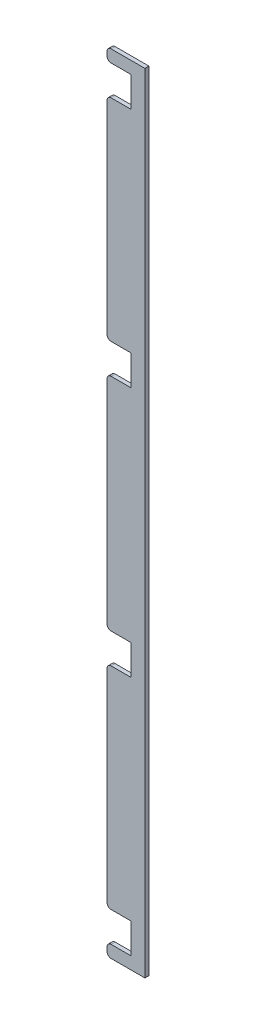
SolidWorks part; units mm, degrees
ref_plane "Front Plane" through (0, 0, 0) normal (0, 0, 1) x (1, 0, 0)
ref_plane "Top Plane" through (0, 0, 0) normal (0, 1, 0) x (1, 0, 0)
ref_plane "Right Plane" through (0, 0, 0) normal (1, 0, 0) x (0, 0, -1)
sketch "Sketch1" plane through (0, 0, 0) normal (0, 0, 1) x (1, 0, 0)
  line L0 (0, -182.5952) -> (-4.5, -182.5952)
  line L2 (0, 13.4048) -> (0, -182.5952)
  line L6 (-4.5, 10.3548) -> (-3.5, 10.3548)
  line L7 (-3.5, 10.3548) -> (-3.5, 2.8548)
  line L9 (-3.5, 2.8548) -> (-4.5, 2.8548)
  line L10 (-4.5, -49.6452) -> (-3.5, -49.6452)
  line L11 (-3.5, -49.6452) -> (-3.5, -57.1452)
  line L12 (-3.5, -57.1452) -> (-4.5, -57.1452)
  line L13 (-4.5, -112.0452) -> (-3.5, -112.0452)
  line L14 (-3.5, -112.0452) -> (-3.5, -119.5452)
  line L15 (-3.5, -119.5452) -> (-4.5, -119.5452)
  line L16 (-4.5, -172.0452) -> (-3.5, -172.0452)
  line L17 (-3.5, -172.0452) -> (-3.5, -179.5452)
  line L18 (-3.5, -179.5452) -> (-4.5, -179.5452)
  line L144 (-8.4, 10.3548) -> (-4.5, 10.3548)
  line L145 (-4.5, 10.3548) -> (-4.5, 2.8548)
  line L146 (-4.5, 2.8548) -> (-8.4, 2.8548)
  line L147 (-9.4, 1.8548) -> (-9.4, -48.6452)
  line L148 (-8.4, -49.6452) -> (-4.5, -49.6452)
  line L149 (-4.5, -49.6452) -> (-4.5, -57.1452)
  line L150 (-4.5, -57.1452) -> (-8.4, -57.1452)
  line L151 (-9.4, -58.1452) -> (-9.4, -111.0452)
  line L152 (-8.4, -112.0452) -> (-4.5, -112.0452)
  line L153 (-4.5, -112.0452) -> (-4.5, -119.5452)
  line L154 (-4.5, -119.5452) -> (-8.4, -119.5452)
  line L155 (-9.4, -120.5452) -> (-9.4, -171.0452)
  line L156 (-8.4, -172.0452) -> (-4.5, -172.0452)
  line L157 (-4.5, -172.0452) -> (-4.5, -179.5452)
  line L158 (-4.5, -179.5452) -> (-8.4, -179.5452)
  line L159 (-9.4, -180.5452) -> (-9.4, -181.5952)
  line L160 (-8.4, -182.5952) -> (-4.5, -182.5952)
  line L186 (0, 13.4048) -> (-8.4, 13.4048)
  line L187 (-9.4, 12.4048) -> (-9.4, 11.3548)
  arc A60 (-8.4, 2.8548) -> (-9.4, 1.8548) centre (-8.4, 1.8548) ccw
  arc A61 (-9.4, -48.6452) -> (-8.4, -49.6452) centre (-8.4, -48.6452) ccw
  arc A62 (-8.4, -57.1452) -> (-9.4, -58.1452) centre (-8.4, -58.1452) ccw
  arc A63 (-9.4, -111.0452) -> (-8.4, -112.0452) centre (-8.4, -111.0452) ccw
  arc A64 (-8.4, -119.5452) -> (-9.4, -120.5452) centre (-8.4, -120.5452) ccw
  arc A65 (-9.4, -171.0452) -> (-8.4, -172.0452) centre (-8.4, -171.0452) ccw
  arc A66 (-8.4, -179.5452) -> (-9.4, -180.5452) centre (-8.4, -180.5452) ccw
  arc A67 (-9.4, -181.5952) -> (-8.4, -182.5952) centre (-8.4, -181.5952) ccw
  arc A78 (-8.4, 13.4048) -> (-9.4, 12.4048) centre (-8.4, 12.4048) ccw
  arc A79 (-9.4, 11.3548) -> (-8.4, 10.3548) centre (-8.4, 11.3548) ccw
extrude "Boss-Extrude1" add sketch "Sketch1" along normal blind 1 contours L2 region at (-4.508, -84.5952, 0)
